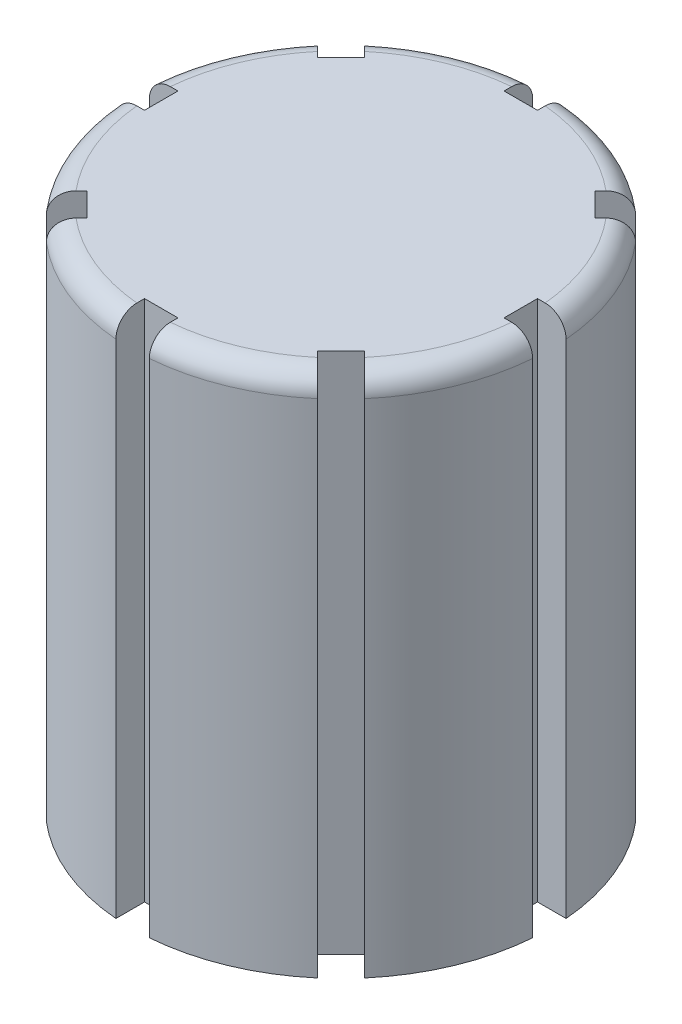
SolidWorks part; units mm, degrees
material "Nickel"
ref_plane "Front Plane" through (0, 0, 0) normal (0, 0, 1) x (1, 0, 0)
ref_plane "Top Plane" through (0, 0, 0) normal (0, 1, 0) x (1, 0, 0)
ref_plane "Right Plane" through (0, 0, 0) normal (1, 0, 0) x (0, 0, -1)
sketch "Sketch1" plane through (0, 0, 0) normal (0, 1, 0) x (1, 0, 0)
  circle A0 centre (0, 0) radius 10
  dimension "D1" = 20
extrude "Boss-Extrude1" add sketch "Sketch1" along normal blind 25
sketch "Sketch2" plane through (0, 0, 0) normal (0, -1, 0) x (1, 0, 0)
  circle A0 centre (0, 0) radius 6.625
  dimension "D1" = 13.25
extrude "Cut-Extrude1" cut sketch "Sketch2" against normal blind 20
chamfer "Chamfer1" distance 1 angle 45 1 edges at (0, 0, -6.625)
sketch "Sketch3" plane through (0, 0, 0) normal (0, -1, 0) x (1, 0, 0)
  circle A0 centre (0, 0) radius 6.625
  dimension "D1" = 13.25
curve "Helix/Spiral1" pitch 2 height 19.5 turns 9.75
ref_plane "Plane2" through (0, 0, 0) normal (1, 0, 0) x (0, 0, -1)
sketch "Sketch5" plane through (0, 0, 0) normal (1, 0, 0) x (0, 0, -1)
  line L0 (6.625, 19.5) -> (8.5483, 19.5) construction
  line L1 (7.5, 19.5) -> (6.5, 18.65)
  line L2 (6.5, 18.65) -> (6.5, 20.1743)
  line L3 (6.5, 20.1743) -> (7.5, 19.5)
  line L4 (10, 25) -> (-10, 25) construction
  spline S0 degree 3 poles (0, 0) (-0.8617, 0.0414) (-2.6038, 0.1251) (-4.8059, 0.25) (-6.2802, 0.375) (-6.7974, 0.5) (-6.2801, 0.625) (-4.8065, 0.75) (-2.6013, 0.875) (0, 1) (2.6013, 1.125) (4.8065, 1.25) (6.28, 1.375) (6.7975, 1.5) (6.28, 1.625) (4.8065, 1.75) (2.6013, 1.875) (0, 2) (-2.6013, 2.125) (-4.8065, 2.25) (-6.28, 2.375) (-6.7975, 2.5) (-6.28, 2.625) (-4.8065, 2.75) (-2.6013, 2.875) (0, 3) (2.6013, 3.125) (4.8065, 3.25) (6.28, 3.375) (6.7975, 3.5) (6.28, 3.625) (4.8065, 3.75) (2.6013, 3.875) (0, 4) (-2.6013, 4.125) (-4.8065, 4.25) (-6.28, 4.375) (-6.7975, 4.5) (-6.28, 4.625) (-4.8065, 4.75) (-2.6013, 4.875) (0, 5) (2.6013, 5.125) (4.8065, 5.25) (6.28, 5.375) (6.7975, 5.5) (6.28, 5.625) (4.8065, 5.75) (2.6013, 5.875) (0, 6) (-2.6013, 6.125) (-4.8065, 6.25) (-6.28, 6.375) (-6.7975, 6.5) (-6.28, 6.625) (-4.8065, 6.75) (-2.6013, 6.875) (0, 7) (2.6013, 7.125) (4.8065, 7.25) (6.28, 7.375) (6.7975, 7.5) (6.28, 7.625) (4.8065, 7.75) (2.6013, 7.875) (0, 8) (-2.6013, 8.125) (-4.8065, 8.25) (-6.28, 8.375) (-6.7975, 8.5) (-6.28, 8.625) (-4.8065, 8.75) (-2.6013, 8.875) (0, 9) (2.6013, 9.125) (4.8065, 9.25) (6.28, 9.375) (6.7975, 9.5) (6.28, 9.625) (4.8065, 9.75) (2.6013, 9.875) (0, 10) (-2.6013, 10.125) (-4.8065, 10.25) (-6.28, 10.375) (-6.7975, 10.5) (-6.28, 10.625) (-4.8065, 10.75) (-2.6013, 10.875) (0, 11) (2.6013, 11.125) (4.8065, 11.25) (6.28, 11.375) (6.7975, 11.5) (6.28, 11.625) (4.8065, 11.75) (2.6013, 11.875) (0, 12) (-2.6013, 12.125) (-4.8065, 12.25) (-6.28, 12.375) (-6.7975, 12.5) (-6.28, 12.625) (-4.8065, 12.75) (-2.6013, 12.875) (0, 13) (2.6013, 13.125) (4.8065, 13.25) (6.28, 13.375) (6.7975, 13.5) (6.28, 13.625) (4.8065, 13.75) (2.6013, 13.875) (0, 14) (-2.6013, 14.125) (-4.8065, 14.25) (-6.28, 14.375) (-6.7975, 14.5) (-6.28, 14.625) (-4.8065, 14.75) (-2.6013, 14.875) (0, 15) (2.6013, 15.125) (4.8065, 15.25) (6.28, 15.375) (6.7975, 15.5) (6.28, 15.625) (4.8065, 15.75) (2.6013, 15.875) (0, 16) (-2.6013, 16.125) (-4.8065, 16.25) (-6.28, 16.375) (-6.7975, 16.5) (-6.28, 16.625) (-4.8065, 16.75) (-2.6013, 16.875) (0, 17) (2.6013, 17.125) (4.8065, 17.25) (6.28, 17.375) (6.7975, 17.5) (6.28, 17.625) (4.8065, 17.75) (2.6013, 17.875) (0, 18) (-2.6013, 18.125) (-4.8065, 18.25) (-6.28, 18.375) (-6.7975, 18.5) (-6.28, 18.625) (-4.8065, 18.75) (-2.6013, 18.875) (0, 19) (2.6013, 19.125) (4.8065, 19.25) (6.28, 19.3749) (6.625, 19.4586) (6.625, 19.5) knots 0 0 0 0 0.00641 0.012821 0.019231 0.025641 0.032051 0.038462 0.044872 0.051282 0.057692 0.064103 0.070513 0.076923 0.083333 0.089744 0.096154 0.102564 0.108974 0.115385 0.121795 0.128205 0.134615 0.141026 0.147436 0.153846 0.160256 0.166667 0.173077 0.179487 0.185897 0.192308 0.198718 0.205128 0.211538 0.217949 0.224359 0.230769 0.237179 0.24359 0.25 0.25641 0.262821 0.269231 0.275641 0.282051 0.288462 0.294872 0.301282 0.307692 0.314103 0.320513 0.326923 0.333333 0.339744 0.346154 0.352564 0.358974 0.365385 0.371795 0.378205 0.384615 0.391026 0.397436 0.403846 0.410256 0.416667 0.423077 0.429487 0.435897 0.442308 0.448718 0.455128 0.461538 0.467949 0.474359 0.480769 0.487179 0.49359 0.5 0.50641 0.512821 0.519231 0.525641 0.532051 0.538462 0.544872 0.551282 0.557692 0.564103 0.570513 0.576923 0.583333 0.589744 0.596154 0.602564 0.608974 0.615385 0.621795 0.628205 0.634615 0.641026 0.647436 0.653846 0.660256 0.666667 0.673077 0.679487 0.685897 0.692308 0.698718 0.705128 0.711538 0.717949 0.724359 0.730769 0.737179 0.74359 0.75 0.75641 0.762821 0.769231 0.775641 0.782051 0.788462 0.794872 0.801282 0.807692 0.814103 0.820513 0.826923 0.833333 0.839744 0.846154 0.852564 0.858974 0.865385 0.871795 0.878205 0.884615 0.891026 0.897436 0.903846 0.910256 0.916667 0.923077 0.929487 0.935897 0.942308 0.948718 0.955128 0.961538 0.967949 0.974359 0.980769 0.987179 0.99359 1 1 1 1 construction
  dimension "D1" = 7.5
  dimension "D2" = 4.8257
  dimension "D3" = 0.85
  dimension "D4" = 6.5
sweep "Cut-Sweep1" cut profiles "Sketch5" path "Helix/Spiral1"
fillet "Fillet1" radius 1 1 edges at (0, 25, 10)
sketch "Sketch6" plane through (0, 0, 0) normal (0, -1, 0) x (1, 0, 0)
  line L0 (5.5154, 6.6468) -> (6.9296, 8.061)
  line L1 (-0.8, 8.6) -> (0.8, 8.6)
  line L2 (-0.8, 8.6) -> (-0.8, 10.6)
  line L3 (-0.8, 10.6) -> (0.8, 10.6)
  line L4 (0.8, 8.6) -> (0.8, 10.6)
  line L5 (6.6468, 5.5154) -> (8.061, 6.9296)
  line L6 (5.5154, 6.6468) -> (6.6468, 5.5154)
  line L7 (6.9296, 8.061) -> (8.061, 6.9296)
  line L8 (8.6, 0.8) -> (10.6, 0.8)
  line L9 (8.6, -0.8) -> (10.6, -0.8)
  line L10 (8.6, 0.8) -> (8.6, -0.8)
  line L11 (10.6, 0.8) -> (10.6, -0.8)
  line L12 (6.6468, -5.5154) -> (8.061, -6.9296)
  line L13 (5.5154, -6.6468) -> (6.9296, -8.061)
  line L14 (6.6468, -5.5154) -> (5.5154, -6.6468)
  line L15 (8.061, -6.9296) -> (6.9296, -8.061)
  line L16 (0.8, -8.6) -> (0.8, -10.6)
  line L17 (-0.8, -8.6) -> (-0.8, -10.6)
  line L18 (0.8, -8.6) -> (-0.8, -8.6)
  line L19 (0.8, -10.6) -> (-0.8, -10.6)
  line L20 (-5.5154, -6.6468) -> (-6.9296, -8.061)
  line L21 (-6.6468, -5.5154) -> (-8.061, -6.9296)
  line L22 (-5.5154, -6.6468) -> (-6.6468, -5.5154)
  line L23 (-6.9296, -8.061) -> (-8.061, -6.9296)
  line L24 (-8.6, -0.8) -> (-10.6, -0.8)
  line L25 (-8.6, 0.8) -> (-10.6, 0.8)
  line L26 (-8.6, -0.8) -> (-8.6, 0.8)
  line L27 (-10.6, -0.8) -> (-10.6, 0.8)
  line L28 (-6.6468, 5.5154) -> (-8.061, 6.9296)
  line L29 (-5.5154, 6.6468) -> (-6.9296, 8.061)
  line L30 (-6.6468, 5.5154) -> (-5.5154, 6.6468)
  line L31 (-8.061, 6.9296) -> (-6.9296, 8.061)
  point P35 (0, 0)
  dimension "D1" = 8.6
  dimension "D2" = 2
  dimension "D3" = 0.8
  dimension "D4" = 1.6
  dimension "D5" = 8
extrude "Cut-Extrude2" cut sketch "Sketch6" against normal up to next
